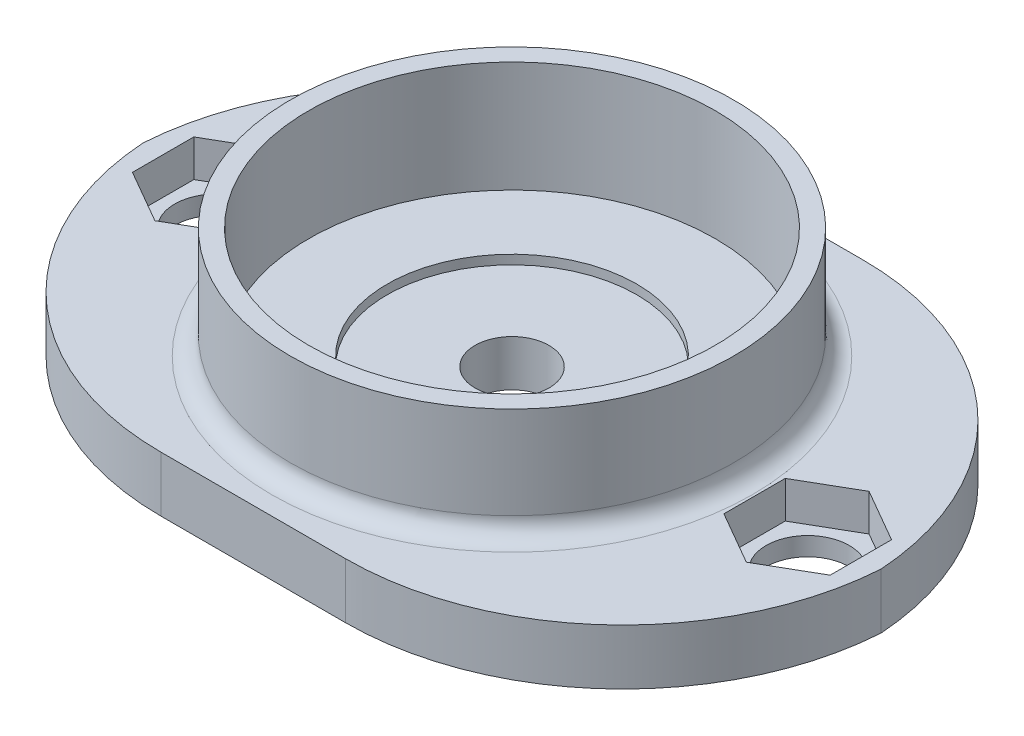
SolidWorks part; units mm, degrees
ref_plane "Front Plane" through (0, 0, 0) normal (0, 0, 1) x (1, 0, 0)
ref_plane "Top Plane" through (0, 0, 0) normal (0, 1, 0) x (1, 0, 0)
ref_plane "Right Plane" through (0, 0, 0) normal (1, 0, 0) x (0, 0, -1)
sketch "Sketch2" plane through (0, 0, 0) normal (0, 1, 0) x (1, 0, 0)
  line L1 (-20, 14) -> (20, 14)
  line L2 (-20, 14) -> (-20, -14)
  line L3 (-20, -14) -> (20, -14)
  line L4 (20, 14) -> (20, -14)
  line L5 (0, -14) -> (0, 14) construction
  line L6 (-20, 0) -> (20, 0) construction
  point P248 (0, 0)
  dimension "D1" = 28
  dimension "D2" = 40
extrude "Boss-Extrude1" add sketch "Sketch2" along normal blind 3
sketch "Sketch3" plane through (0, 3, 0) normal (0, 1, 0) x (1, 0, 0)
  circle A0 centre (0, 0) radius 12
  circle A1 centre (0, 0) radius 11
  dimension "D1" = 22
  dimension "D2" = 1
extrude "Boss-Extrude2" add sketch "Sketch3" along normal blind 6
sketch "Sketch4" plane through (0, 3, 0) normal (0, 1, 0) x (1, 0, 0)
  line L0 (-4.95, 0) -> (4.95, 0) construction
  line L1 (-16, 3.3198) -> (-18.875, 1.6599)
  line L2 (-18.875, 1.6599) -> (-18.875, -1.6599)
  line L3 (-18.875, -1.6599) -> (-16, -3.3198)
  line L4 (-16, -3.3198) -> (-13.125, -1.6599)
  line L5 (-13.125, -1.6599) -> (-13.125, 1.6599)
  line L6 (-13.125, 1.6599) -> (-16, 3.3198)
  line L7 (0, -4.95) -> (0, 4.95) construction
  circle A0 centre (-16, 0) radius 2.875 construction
  dimension "D1" = 5.75
  dimension "D2" = 16
extrude "Cut-Extrude1" cut sketch "Sketch4" against normal blind 2
hole_wizard "M4 Clearance Hole1" positions "Sketch7" profile "Sketch6" hole size "M4" standard "ISO"
sketch "Sketch7" plane through (0, 1, 0) normal (0, 1, 0) x (1, 0, 0)
  line L0 (-4.95, 0) -> (4.95, 0) construction
  line L1 (0, -4.95) -> (0, 4.95) construction
  point P0 (-16, 0)
  dimension "D1" = 16
sketch "Sketch6" plane through (-16, 1, 0) normal (1, 0, 0) x (0, 0, 1)
  line L0 (0, 0) -> (0, 3.3519)
  line L1 (0, 3.3519) -> (2.25, 2)
  line L2 (2.25, 2) -> (2.25, 0)
  line L5 (2.25, 0) -> (0, 0)
  line L10 (0, 3.3519) -> (-2.25, 2) construction
  line L11 (0, -6.35) -> (0, 107.95) construction
  dimension "Hole Dia." = 4.5
  dimension "Hole Depth" = 2
  dimension "Drill Angle" = 118
mirror "Mirror1" about plane through (0, 0, 0) normal (1, 0, 0) of "Cut-Extrude1", "M4 Clearance Hole1"
fillet "Fillet1" radius 1 1 edges at (0, 3, 12)
fillet "Fillet2" radius 15 4 edges at (-20, 1.5, -14) (20, 1.5, 14) (-20, 1.5, 14) (20, 1.5, -14)
sketch "Sketch8" plane through (0, 3, 0) normal (0, 1, 0) x (1, 0, 0)
  circle A0 centre (0, 0) radius 6.75
  dimension "D1" = 13.5
extrude "Cut-Extrude2" cut sketch "Sketch8" against normal blind 0.5
sketch "Sketch9" plane through (0, 2.5, 0) normal (0, 1, 0) x (1, 0, 0)
  circle A0 centre (0, 0) radius 2
  dimension "D1" = 4
extrude "Cut-Extrude3" cut sketch "Sketch9" against normal through all
